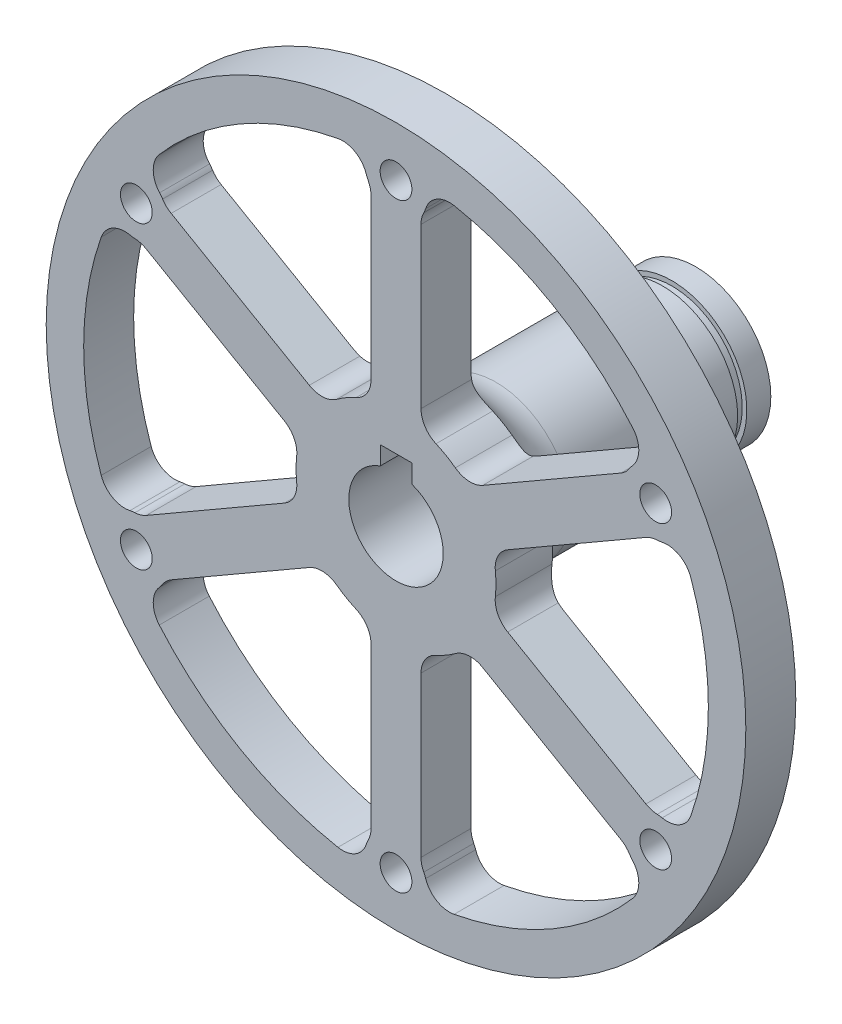
SolidWorks part; units mm, degrees
material "6061-T6 (SS)"
ref_plane "Front Plane" through (0, 0, 0) normal (0, 0, 1) x (1, 0, 0)
ref_plane "Top Plane" through (0, 0, 0) normal (0, 1, 0) x (1, 0, 0)
ref_plane "Right Plane" through (0, 0, 0) normal (1, 0, 0) x (0, 0, -1)
sketch "Sketch1" plane through (0, 0, 0) normal (0, 0, 1) x (1, 0, 0)
  circle A0 centre (0, 0) radius 9.525
  dimension "D1" = 19.05
extrude "Boss-Extrude1" add sketch "Sketch1" along normal blind 31.75
sketch "Sketch2" plane through (0, 0, 31.75) normal (0, 0, 1) x (1, 0, 0)
  circle A0 centre (0, 0) radius 44.45
  dimension "D1" = 88.9
extrude "Boss-Extrude2" add sketch "Sketch2" along normal blind 6.35
fillet "Fillet1" radius 6.35 1 edges at (9.525, 0, 31.75)
hole_wizard "#10-32 Tapped Hole1" positions "Sketch4" profile "Sketch3" tap size "#10-32" standard "Ansi Inch" end condition through all
sketch "Sketch4" plane through (0, 0, 38.1) normal (0, 0, 1) x (1, 0, 0)
  line L0 (0, 0) -> (0, 44.45)
  circle A0 centre (0, 0) radius 44.45 construction
  point P0 (0, 38.1)
  point P16 (32.9956, 19.05)
  point P17 (32.9956, -19.05)
  point P18 (0, -38.1)
  point P19 (-32.9956, -19.05)
  point P20 (-32.9956, 19.05)
  dimension "D1" = 38.1
  dimension "D2" = 6
sketch "Sketch3" plane through (0, 38.1, 38.1) normal (1, 0, 0) x (0, -1, 0)
  line L0 (0, 0) -> (0, 38.1)
  line L1 (0, 38.1) -> (2.0193, 38.1)
  line L2 (2.0193, 38.1) -> (2.0193, 0)
  line L5 (2.0193, 0) -> (0, 0)
  line L11 (0, -6.35) -> (0, 107.95) construction
  dimension "Thru Tap Drill Dia." = 4.0386
  dimension "Thru Tap Drill Depth" = 38.1
cosmetic thread "Hole Thread1" parameters "D2"=4.826
cosmetic thread "Hole Thread2" parameters "D2"=4.826
cosmetic thread "Hole Thread3" parameters "D2"=4.826
cosmetic thread "Hole Thread4" parameters "D2"=4.826
cosmetic thread "Hole Thread5" parameters "D2"=4.826
cosmetic thread "Hole Thread6" parameters "D2"=4.826
sketch "Sketch5" plane through (0, 0, 38.1) normal (0, 0, 1) x (1, 0, 0)
  line L0 (0, 0) -> (0, 38.1)
  line L1 (0, 0) -> (32.9956, 19.05)
  line L2 (3.175, 34.8273) -> (3.175, 14.5497)
  line L3 (28.5738, 20.1633) -> (11.0129, 10.0245)
  line L4 (0, 0) -> (32.9956, 19.05)
  line L5 (0, 0) -> (32.9956, -19.05)
  line L6 (31.7488, 14.664) -> (14.1879, 4.5252)
  line L7 (31.7488, -14.664) -> (14.1879, -4.5252)
  line L8 (0, 0) -> (32.9956, 19.05)
  line L9 (0, 0) -> (32.9956, -19.05)
  line L10 (0, 0) -> (0, -38.1)
  line L11 (28.5738, -20.1633) -> (11.0129, -10.0245)
  line L12 (3.175, -34.8273) -> (3.175, -14.5497)
  line L13 (0, 0) -> (32.9956, -19.05)
  line L14 (0, 0) -> (0, -38.1)
  line L15 (0, 0) -> (-32.9956, -19.05)
  line L16 (-3.175, -34.8273) -> (-3.175, -14.5497)
  line L17 (-28.5738, -20.1633) -> (-11.0129, -10.0245)
  line L18 (0, 0) -> (0, -38.1)
  line L19 (0, 0) -> (-32.9956, -19.05)
  line L20 (0, 0) -> (-32.9956, 19.05)
  line L21 (0, 0) -> (0, 38.1)
  line L22 (-31.7488, -14.664) -> (-14.1879, -4.5252)
  line L23 (-31.7488, 14.664) -> (-14.1879, 4.5252)
  line L24 (-11.9719, -10.5781) -> (4.8786, -0.8495) [skipped]
  line L25 (29.5524, 20.7283) -> (12.7009, 10.999) [skipped]
  line L26 (-15.1469, 5.0789) -> (1.7036, -4.6498) [skipped]
  line L27 (-78.1965, 48.813) -> (-61.345, 39.0838) [skipped]
  line L28 (15.1469, -5.0789) -> (-1.7036, 4.6498) [skipped]
  line L29 (-32.7274, 15.229) -> (-15.8759, 5.4998) [skipped]
  line L30 (3.175, -15.657) -> (3.175, 3.8003) [skipped]
  line L31 (-3.175, 35.9572) -> (-3.175, 16.4988) [skipped]
  line L32 (0, 0) -> (-32.9956, 19.05) [skipped]
  line L33 (0, 0) -> (-32.9956, -19.05) [skipped]
  line L34 (0, 0) -> (-32.9956, 19.05) [skipped]
  line L35 (0, 0) -> (32.9956, -19.05) [skipped]
  line L36 (-3.175, 18.6757) -> (-3.175, 38.133) [skipped]
  line L37 (35.0037, 16.5432) -> (50.0753, 25.2448) [skipped]
  line L38 (0, 0) -> (32.9956, -19.05) [skipped]
  line L39 (0, 0) -> (0, -38.1) [skipped]
  line L40 (0, 0) -> (-32.9956, -19.05) [skipped]
  line L41 (0, 0) -> (32.9956, 19.05) [skipped]
  line L42 (0, 0) -> (0, -38.1) [skipped]
  line L43 (0, 0) -> (-32.9956, -19.05)
  line L44 (0, 0) -> (-32.9956, 19.05)
  line L45 (0, 0) -> (0, 38.1)
  line L46 (-28.5738, 20.1633) -> (-11.0129, 10.0245)
  line L47 (-3.175, 34.8273) -> (-3.175, 14.5497)
  line L48 (0, 0) -> (-32.9956, 19.05)
  arc A0 (30.0816, 25.8882) -> (7.379, 38.9955) centre (0, 0) ccw
  arc A1 (30.0397, 21.6984) -> (29.6571, 21.1961) centre (32.9956, 19.05) ccw
  arc A2 (7.5403, 10.2193) -> (5.08, 11.6397) centre (0, 0) ccw
  arc A3 (3.175, 14.5497) -> (5.08, 11.6397) centre (6.35, 14.5497) ccw
  arc A4 (11.0129, 10.0245) -> (7.5403, 10.2193) centre (9.4254, 12.7741) cw
  arc A5 (28.5738, 20.1633) -> (29.6571, 21.1961) centre (26.9863, 22.9129) ccw
  arc A6 (30.0816, 25.8882) -> (30.0397, 21.6984) centre (27.675, 23.8171) cw
  arc A7 (3.175, 34.8273) -> (3.5278, 36.2818) centre (6.35, 34.8273) cw
  arc A8 (7.379, 38.9955) -> (3.7715, 36.8644) centre (6.7887, 35.8758) ccw
  arc A9 (37.4606, -13.1073) -> (37.4606, 13.1073) centre (0, 0) ccw
  arc A10 (33.8112, -15.166) -> (33.1849, -15.0858) centre (32.9956, -19.05) ccw
  arc A11 (12.6203, -1.4205) -> (12.6203, 1.4205) centre (0, 0) ccw
  arc A12 (14.1879, 4.5252) -> (12.6203, 1.4205) centre (15.7754, 1.7756) ccw
  arc A13 (14.1879, -4.5252) -> (12.6203, -1.4205) centre (15.7754, -1.7756) cw
  arc A14 (31.7488, -14.664) -> (33.1849, -15.0858) centre (33.3363, -11.9144) ccw
  arc A15 (37.4606, -13.1073) -> (33.8112, -15.166) centre (34.4637, -12.0587) cw
  arc A16 (31.7488, 14.664) -> (33.1849, 15.0858) centre (33.3363, 11.9144) cw
  arc A17 (37.4606, 13.1073) -> (33.8112, 15.166) centre (34.4637, 12.0587) ccw
  arc A18 (33.1849, 15.0858) -> (33.8112, 15.166) centre (32.9956, 19.05) ccw
  arc A19 (7.379, -38.9955) -> (30.0816, -25.8882) centre (0, 0) ccw
  arc A20 (3.7715, -36.8644) -> (3.5278, -36.2818) centre (0, -38.1) ccw
  arc A21 (5.08, -11.6397) -> (7.5403, -10.2193) centre (0, 0) ccw
  arc A22 (11.0129, -10.0245) -> (7.5403, -10.2193) centre (9.4254, -12.7741) ccw
  arc A23 (3.175, -14.5497) -> (5.08, -11.6397) centre (6.35, -14.5497) cw
  arc A24 (3.175, -34.8273) -> (3.5278, -36.2818) centre (6.35, -34.8273) ccw
  arc A25 (7.379, -38.9955) -> (3.7715, -36.8644) centre (6.7887, -35.8758) cw
  arc A26 (28.5738, -20.1633) -> (29.6571, -21.1961) centre (26.9863, -22.9129) cw
  arc A27 (30.0816, -25.8882) -> (30.0397, -21.6984) centre (27.675, -23.8171) ccw
  arc A28 (29.6571, -21.1961) -> (30.0397, -21.6984) centre (32.9956, -19.05) ccw
  arc A29 (-30.0816, -25.8882) -> (-7.379, -38.9955) centre (0, 0) ccw
  arc A30 (-30.0397, -21.6984) -> (-29.6571, -21.1961) centre (-32.9956, -19.05) ccw
  arc A31 (-7.5403, -10.2193) -> (-5.08, -11.6397) centre (0, 0) ccw
  arc A32 (-3.175, -14.5497) -> (-5.08, -11.6397) centre (-6.35, -14.5497) ccw
  arc A33 (-11.0129, -10.0245) -> (-7.5403, -10.2193) centre (-9.4254, -12.7741) cw
  arc A34 (-28.5738, -20.1633) -> (-29.6571, -21.1961) centre (-26.9863, -22.9129) ccw
  arc A35 (-30.0816, -25.8882) -> (-30.0397, -21.6984) centre (-27.675, -23.8171) cw
  arc A36 (-3.175, -34.8273) -> (-3.5278, -36.2818) centre (-6.35, -34.8273) cw
  arc A37 (3.5278, 36.2818) -> (3.7715, 36.8644) centre (0, 38.1) ccw
  arc A38 (-7.379, -38.9955) -> (-3.7715, -36.8644) centre (-6.7887, -35.8758) ccw
  arc A39 (-3.5278, -36.2818) -> (-3.7715, -36.8644) centre (0, -38.1) ccw
  arc A40 (-37.4606, 13.1073) -> (-37.4606, -13.1073) centre (0, 0) ccw
  arc A41 (-33.8112, 15.166) -> (-33.1849, 15.0858) centre (-32.9956, 19.05) ccw
  arc A42 (-12.6203, 1.4205) -> (-12.6203, -1.4205) centre (0, 0) ccw
  arc A43 (-14.1879, -4.5252) -> (-12.6203, -1.4205) centre (-15.7754, -1.7756) ccw
  arc A44 (-14.1879, 4.5252) -> (-12.6203, 1.4205) centre (-15.7754, 1.7756) cw
  arc A45 (-31.7488, 14.664) -> (-33.1849, 15.0858) centre (-33.3363, 11.9144) ccw
  arc A46 (-37.4606, 13.1073) -> (-33.8112, 15.166) centre (-34.4637, 12.0587) cw
  arc A47 (-31.7488, -14.664) -> (-33.1849, -15.0858) centre (-33.3363, -11.9144) cw
  arc A48 (-37.4606, -13.1073) -> (-33.8112, -15.166) centre (-34.4637, -12.0587) ccw
  arc A49 (-33.1849, -15.0858) -> (-33.8112, -15.166) centre (-32.9956, -19.05) ccw
  arc A50 (-7.379, 38.9955) -> (-30.0816, 25.8882) centre (0, 0) ccw
  arc A51 (-3.7715, 36.8644) -> (-3.5278, 36.2818) centre (0, 38.1) ccw
  arc A52 (-5.08, 11.6397) -> (-7.5403, 10.2193) centre (0, 0) ccw
  arc A53 (-11.0129, 10.0245) -> (-7.5403, 10.2193) centre (-9.4254, 12.7741) ccw
  arc A54 (-3.175, 14.5497) -> (-5.08, 11.6397) centre (-6.35, 14.5497) cw
  arc A55 (-3.175, 34.8273) -> (-3.5278, 36.2818) centre (-6.35, 34.8273) ccw
  arc A56 (-7.379, 38.9955) -> (-3.7715, 36.8644) centre (-6.7887, 35.8758) cw
  arc A57 (-28.5738, 20.1633) -> (-29.6571, 21.1961) centre (-26.9863, 22.9129) cw
  arc A58 (-30.0816, 25.8882) -> (-30.0397, 21.6984) centre (-27.675, 23.8171) ccw
  arc A59 (-29.6571, 21.1961) -> (-30.0397, 21.6984) centre (-32.9956, 19.05) ccw
  arc A72 (2.3622, 36.0198) -> (6.9022, 39.0827) centre (5.5309, 36.2191) cw [skipped]
  arc A73 (31.776, 22.8577) -> (31.0329, 24.9409) centre (28.6012, 22.8994) ccw [skipped]
  arc A74 (36.3099, 15.63) -> (37.2977, 13.5639) centre (34.1321, 13.3196) cw [skipped]
  arc A75 (36.31, -15.63) -> (37.2977, -13.5639) centre (34.1321, -13.3197) ccw [skipped]
  arc A76 (-7.5403, -10.2193) -> (-5.08, -11.6397) centre (0, 0) ccw [skipped]
  arc A77 (-3.175, -14.5497) -> (-5.08, -11.6397) centre (-6.35, -14.5497) ccw [skipped]
  arc A78 (-11.0129, -10.0245) -> (-7.5403, -10.2193) centre (-9.4254, -12.7741) cw [skipped]
  arc A79 (-37.2977, 13.5639) -> (-37.2977, -13.5639) centre (0, 0) ccw [skipped]
  arc A80 (-12.6203, 1.4205) -> (-12.6203, -1.4205) centre (0, 0) ccw [skipped]
  arc A81 (-14.1879, -4.5252) -> (-12.6203, -1.4205) centre (-15.7754, -1.7756) ccw [skipped]
  arc A82 (-14.1879, 4.5252) -> (-12.6203, 1.4205) centre (-15.7754, 1.7756) cw [skipped]
  arc A83 (-32.3741, 15.9636) -> (-37.2977, 13.5639) centre (-34.1321, 13.3197) ccw [skipped]
  arc A84 (-32.3751, -15.9642) -> (-37.2977, -13.5639) centre (-34.1321, -13.3196) cw [skipped]
  arc A85 (-5.08, 11.6397) -> (-7.5403, 10.2193) centre (0, 0) ccw [skipped]
  arc A86 (-11.0129, 10.0245) -> (-7.5403, 10.2193) centre (-9.4254, 12.7741) ccw [skipped]
  arc A87 (-3.175, 14.5497) -> (-5.08, 11.6397) centre (-6.35, 14.5497) cw [skipped]
  arc A92 (14.1879, -4.5252) -> (12.6203, -1.4205) centre (15.7754, -1.7756) cw [skipped]
  arc A93 (6.9022, -39.0827) -> (30.3955, -25.5188) centre (0, 0) ccw [skipped]
  arc A94 (5.08, -11.6397) -> (7.5403, -10.2193) centre (0, 0) ccw [skipped]
  arc A95 (11.0129, -10.0245) -> (7.5403, -10.2193) centre (9.4254, -12.7741) ccw [skipped]
  arc A96 (3.175, -14.5497) -> (5.08, -11.6397) centre (6.35, -14.5497) cw [skipped]
  arc A97 (2.3622, -36.0186) -> (6.9022, -39.0827) centre (5.5309, -36.2191) ccw [skipped]
  arc A98 (30.0129, -20.0556) -> (30.3955, -25.5188) centre (28.6012, -22.8995) cw [skipped]
  arc A99 (-30.3955, -25.5188) -> (-6.9022, -39.0827) centre (0, 0) ccw [skipped]
  arc A100 (-30.0119, -20.055) -> (-30.3955, -25.5188) centre (-28.6012, -22.8994) ccw [skipped]
  arc A101 (-2.3622, -36.0198) -> (-6.9022, -39.0827) centre (-5.5309, -36.2191) cw [skipped]
  arc A105 (-30.0129, 20.0556) -> (-30.3955, 25.5188) centre (-28.6012, 22.8995) cw [skipped]
  arc A107 (-6.9022, 39.0827) -> (-30.3955, 25.5188) centre (0, 0) ccw [skipped]
  arc A108 (-2.3622, 36.0186) -> (-6.9022, 39.0827) centre (-5.5309, 36.2191) ccw [skipped]
  arc A110 (12.6203, -1.4205) -> (12.6203, 1.4205) centre (0, 0) ccw [skipped]
  arc A111 (37.2977, -13.5639) -> (36.4288, 15.7493) centre (0, 0) ccw [skipped]
  arc A113 (14.1879, 4.5252) -> (12.6203, 1.4205) centre (15.7754, 1.7756) ccw [skipped]
  dimension "D1" = 12.7
  dimension "D6" = 7.9375
  dimension "D2" = 79.375
  dimension "D5" = 3.175
  dimension "D8" = 7.9375
  dimension "D9" = 3.175
  dimension "D3" = 3.175
  dimension "D4" = 3.175
  dimension "D7" = 6
extrude "Cut-Extrude2" cut sketch "Sketch5" against normal through all contours A37 A7 L2 A3 A2 A4 L3 A5 A1 A6 A0 A8 | A59 A57 L46 A53 A52 A54 L47 A55 A51 A56 A50 A58 | A49 A47 L22 A43 A42 A44 L23 A45 A41 A46 A40 A48 | A39 A36 L16 A32 A31 A33 L17 A34 A30 A35 A29 A38 | A28 A26 L11 A22 A21 A23 L12 A24 A20 A25 A19 A27 | A18 A16 L6 A12 A11 A13 L7 A14 A10 A15 A9 A17
sketch "Sketch6" plane through (0, 0, 0) normal (0, 0, -1) x (-1, 0, 0)
  line L0 (-2, 5.6569) -> (-2, 8)
  line L1 (-2, 8) -> (2, 8)
  line L2 (2, 8) -> (2, 5.6569)
  circle A0 centre (0, 0) radius 6
  dimension "D1" = 12
  dimension "D2" = 2
  dimension "D3" = 2
  dimension "D4" = 8
extrude "Cut-Extrude3" cut sketch "Sketch6" against normal through all contours A0 | A0 L2 L1 L0 region at (0, 6.941, 0) region at (0, 0, 0)
sketch "Sketch7" plane through (0, 0, 0) normal (0, 1, 0) x (1, 0, 0)
  line L0 (9.525, 0) -> (-9.525, 0) construction
  line L1 (-10.5283, -4.2164) -> (-8.9408, -4.2164)
  line L2 (-10.5283, -4.2164) -> (-10.5283, -3.048)
  line L3 (-10.5283, -3.048) -> (-8.9408, -3.048)
  line L4 (-8.9408, -4.2164) -> (-8.9408, -3.048)
  line L5 (0, 0) -> (0, -31.75) construction
  dimension "D1" = 8.9408
  dimension "D2" = 1.5875
  dimension "D3" = 1.1684
  dimension "D4" = 3.048
  dimension "D5" = 31.75
revolve "Cut-Revolve1" cut sketch "Sketch7" angle 360 about L5
